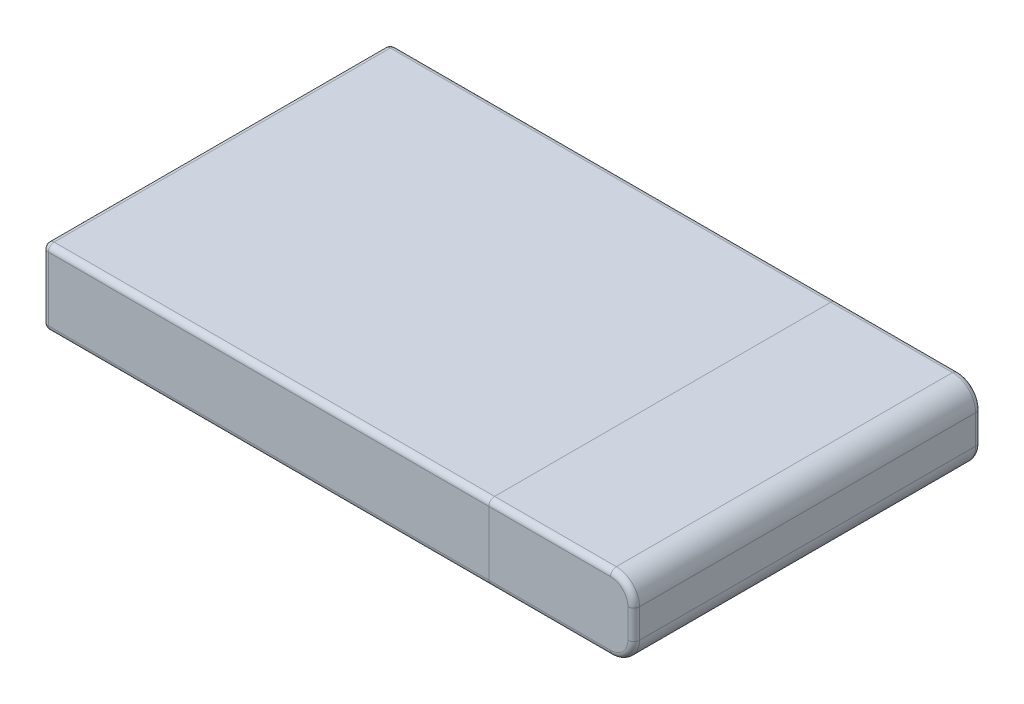
SolidWorks part; units mm, degrees
ref_plane "Front Plane" through (0, 0, 0) normal (0, 0, 1) x (1, 0, 0)
ref_plane "Top Plane" through (0, 0, 0) normal (0, 1, 0) x (1, 0, 0)
ref_plane "Right Plane" through (0, 0, 0) normal (1, 0, 0) x (0, 0, -1)
sketch "Sketch1" plane through (0, 0, 0) normal (0, 1, 0) x (1, 0, 0)
  line L0 (-19.25, -15) -> (19.25, -15)
  line L1 (-19.25, -15) -> (-19.25, 15)
  line L2 (19.25, -15) -> (19.25, 15)
  line L3 (-19.25, 15) -> (19.25, 15)
  line L4 (-19.25, -15) -> (19.25, 15) construction
  line L5 (19.25, -15) -> (-19.25, 15) construction
  point P1 (0, 0)
  dimension "D1" = 38.5
  dimension "D2" = 30
extrude "Boss-Extrude1" add sketch "Sketch1" along normal blind 3.25 and the other way blind 3.25
sketch "Sketch4" plane through (19.25, 0, 0) normal (1, 0, 0) x (0, 0, -1)
  line L1 (-15, -3.25) -> (15, -3.25)
  line L2 (-15, -3.25) -> (-15, 3.25)
  line L3 (-15, 3.25) -> (15, 3.25)
  line L4 (15, -3.25) -> (15, 3.25)
extrude "Boss-Extrude4" add sketch "Sketch4" along normal blind 12.5 separate body
fillet "Fillet1" radius 2 2 edges at (31.75, -3.25, 0) (31.75, 3.25, 0)
fillet "Fillet3" radius 0.5 10 edges at (24.5, -3.25, 15) (31.1642, -2.6642, 15) (31.75, 0, 15) (31.1642, 2.6642, 15) (24.5, -3.25, -15) (31.1642, -2.6642, -15) (31.75, 0, -15) (31.1642, 2.6642, -15) (24.5, 3.25, 15) (24.5, 3.25, -15)
fillet "Fillet4" radius 0.5 8 edges at (-19.25, 0, 15) (-19.25, 3.25, 0) (-19.25, 0, -15) (-19.25, -3.25, 0) (0, -3.25, -15) (0, 3.25, -15) (0, -3.25, 15) (0, 3.25, 15)
